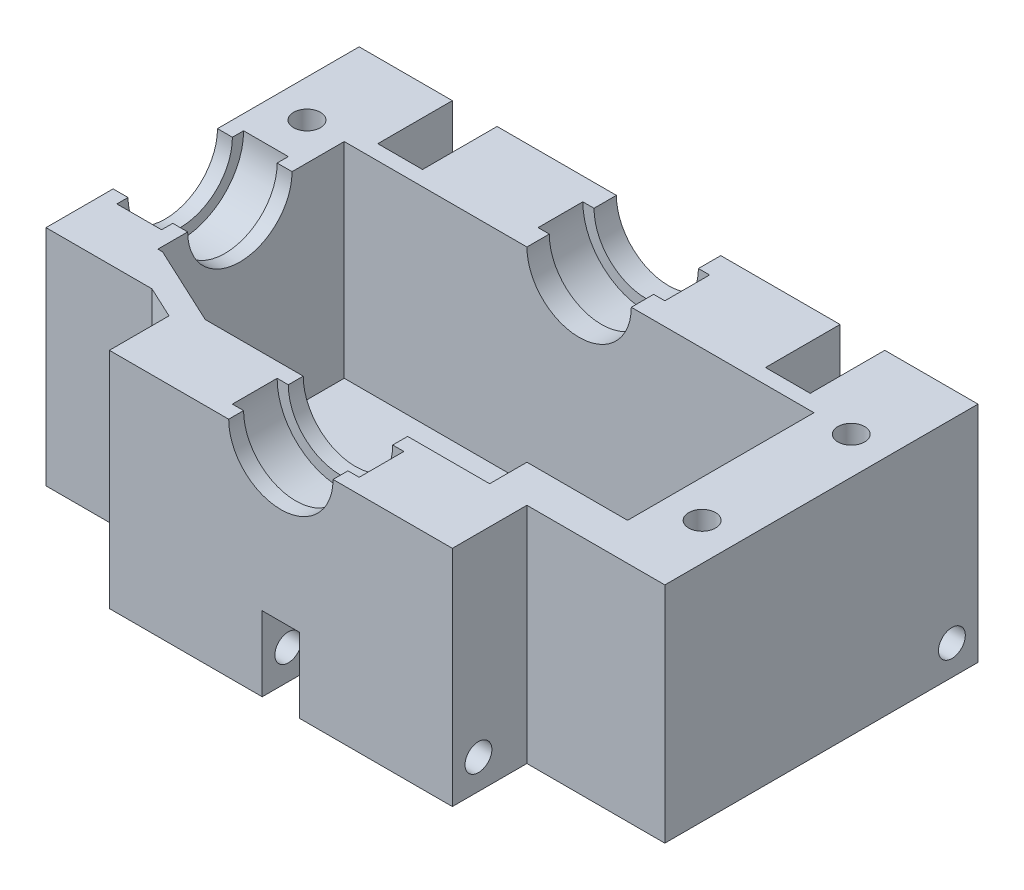
SolidWorks part; units mm, degrees
note: The reader was unsure of these and kept them because the rebuilt part matched: shared geometry of "Sketch1<4>", "Sketch3<4>", "Sketch17<3>".
material "PLA"
ref_plane "Front Plane" through (0, 0, 0) normal (0, 0, 1) x (1, 0, 0)
ref_plane "Top Plane" through (0, 0, 0) normal (0, 1, 0) x (1, 0, 0)
ref_plane "Right Plane" through (0, 0, 0) normal (1, 0, 0) x (0, 0, -1)
sketch "Sketch1" plane through (0, 0, 0) normal (0, 1, 0) x (1, 0, 0)
  line L0 (-41.5, 12) -> (41.5, 12)
  line L1 (41.5, 12) -> (41.5, -15)
  line L2 (41.5, -15) -> (31.5, -15) construction
  line L4 (23, -40) -> (-23, -40)
  line L5 (-23, -40) -> (-23, -30)
  line L6 (-23, -15) -> (-31.5, -15) construction
  line L7 (-41.5, -15) -> (-41.5, 12)
  line L8 (-31.5, 0) -> (-31.5, -10)
  line L9 (-31.5, -10) -> (-18, -10) construction
  line L10 (-18, -25) -> (-18, -30)
  line L11 (-18, -30) -> (18, -30)
  line L12 (18, -30) -> (18, -25)
  line L13 (18, -10) -> (31.5, -10) construction
  line L14 (31.5, -10) -> (31.5, 0)
  line L15 (31.5, 0) -> (-31.5, 0)
  line L16 (0, 31.084) -> (0, 48.5118) construction
  line L17 (-10, -35) -> (10, -35) construction
  line L18 (-10, 6) -> (10, 6) construction
  line L23 (23, -30) -> (41.5, -30)
  line L24 (41.5, -30) -> (41.5, -15)
  line L25 (23, -30) -> (23, -40)
  line L26 (31.5, -10) -> (31.5, -25)
  line L27 (31.5, -25) -> (18, -25)
  line L28 (-41.5, -15) -> (-41.5, -30)
  line L29 (-41.5, -30) -> (-23, -30)
  line L30 (-31.5, -10) -> (-31.5, -25)
  line L31 (-31.5, -25) -> (-18, -25)
  line L32 (-31.5, -15) -> (-41.5, -15) construction
  line L33 (-18, -10) -> (-18, -25) construction
  line L34 (-23, -25) -> (-23, -15) construction
  line L35 (-23, -30) -> (-23, -25) construction
  line L36 (31.5, -15) -> (23, -15) construction
  line L37 (23, -15) -> (23, -25) construction
  line L38 (18, -25) -> (18, -10) construction
  line L39 (23, -25) -> (23, -30) construction
  point P17 (0, -40)
  point P19 (0, -30)
  point P20 (0, 0)
  point P21 (0, 12)
  point P22 (-10, 6)
  point P23 (10, 6)
  point P24 (10, -35)
  point P25 (-10, -35)
  dimension "D1" = 63
  dimension "D2" = 10
  dimension "D3" = 12
  dimension "D4" = 10
  dimension "D5" = 10
  dimension "D6" = 5
  dimension "D7" = 5
  dimension "D8" = 10
  dimension "D9" = 20
  dimension "D10" = 36
  dimension "D11" = 10
  dimension "D13" = 5
extrude "Boss-Extrude1" add sketch "Sketch1" along normal blind 30 contours L0 L1 L24 L23 L25 L4 L5 L29 L28 L7
extrude "Cut-Extrude2" cut sketch "Sketch1<4>" against normal blind 27.5 from surface contours L11 L16 L15 L8 L9 L10 | L16 L11 L12 L13 L14 L15
sketch "Sketch1<4>" plane through (0, 0, 0) normal (0, 1, 0) x (1, 0, 0) same geometry as "Sketch1"
sketch "Sketch3" plane through (0, 0, 40) normal (0, 0, 1) x (1, 0, 0)
  line L0 (23, 30) -> (-23, 30) construction
  circle A0 centre (0, 30) radius 8.5
  circle A1 centre (0, 30) radius 7
  line M3 (23, 30) -> (-23, 30)
  dimension "D1" = 17
  dimension "D2" = 14
extrude "Cut-Extrude3" cut sketch "Sketch3" against normal blind 6 from offset 2 contours A0 offset against normal yes
sketch "Sketch4" plane through (0, 0, -12) normal (0, 0, -1) x (-1, 0, 0)
  line L2 (41.5, 30) -> (-41.5, 30) construction
  circle A0 centre (0, 30) radius 8.5
  circle A1 centre (0, 30) radius 6.5
  dimension "D1" = 17
  dimension "D2" = 13
extrude "Cut-Extrude4" cut sketch "Sketch4" against normal blind 6 from offset 3 contours A0 offset against normal yes
extrude "Cut-Extrude6" cut sketch "Sketch3<4>" against normal through all contours A1 M3 | A1 M3
sketch "Sketch3<4>" plane through (0, 0, 40) normal (0, 0, 1) x (1, 0, 0) same geometry as "Sketch3"
sketch "Sketch16" plane through (0, 0, -12) normal (0, 0, -1) x (-1, 0, 0)
  line L0 (23, 30) -> (23, 0) construction
  line L1 (29, 30) -> (29, 0)
  line L3 (-23, 30) -> (-23, 0)
  line L5 (-7, 30) -> (-41.5, 30)
  line L6 (-41.5, 30) -> (-41.5, 0)
  line L7 (-41.5, 0) -> (41.5, 0)
  line L8 (41.5, 0) -> (41.5, 30)
  line L9 (41.5, 30) -> (7, 30)
  line L10 (-7, 30) -> (-41.5, 30)
  line L11 (-41.5, 30) -> (-41.5, 0)
  line L12 (-41.5, 0) -> (41.5, 0)
  line L13 (41.5, 0) -> (41.5, 30)
  line L14 (41.5, 30) -> (7, 30)
  line L15 (-29, 30) -> (-29, 0)
  line L16 (-23, 30) -> (-23, 0) construction
  line L18 (23, 30) -> (23, 0)
  arc A1 (-7, 30) -> (7, 30) centre (0, 30) ccw
  arc A2 (-7, 30) -> (7, 30) centre (0, 30) ccw
  dimension "D2" = 6
  dimension "D3" = 6
  dimension "D1" = 0
extrude "Cut-Extrude7" cut sketch "Sketch16" against normal blind 10
sketch "Sketch17" plane through (-41.5, 0, 0) normal (1, 0, 0) x (0, 0, -1)
  line L0 (12, 30) -> (-30, 30) construction
  circle A0 centre (-14, 30) radius 8.5
  circle A1 centre (-14, 30) radius 7
  line M14 (-30, 30) -> (12, 30)
  dimension "D1" = 17
  dimension "D2" = 14
  dimension "D3" = 26
extrude "Cut-Extrude8" cut sketch "Sketch17" along normal blind 6 from offset 2 contours A0
extrude "Cut-Extrude9" cut sketch "Sketch17<3>" along normal up to surface (10 mm away) contours A1 M14 | A1 M14 up to face at (-31.5, 16.25, 12.5)
sketch "Sketch17<3>" plane through (-41.5, 0, 0) normal (1, 0, 0) x (0, 0, -1) same geometry as "Sketch17"
chamfer "Chamfer1" distance 2 angle 65 1 edges at (-23, 15, 30)
chamfer "Chamfer2" distance 6 angle 65 1 edges at (-18, 16.25, 25)
sketch "Sketch19" plane through (0, 0, 0) normal (0, -1, 0) x (1, 0, 0)
  line L1 (2.5, -12) -> (-2.5, -12)
  line L2 (2.5, -12) -> (2.5, -5)
  line L3 (2.5, -5) -> (-2.5, -5)
  line L4 (-2.5, -12) -> (-2.5, -5)
  line L6 (-2.5, 40) -> (2.5, 40)
  line L7 (-2.5, 40) -> (-2.5, 33)
  line L8 (-2.5, 33) -> (2.5, 33)
  line L9 (2.5, 40) -> (2.5, 33)
  line L10 (23, 40) -> (-23, 40) construction
  line L11 (-23, -12) -> (23, -12) construction
  point P20 (0, 33)
  point P23 (0, -5)
  dimension "D1" = 5
  dimension "D2" = 7
  dimension "D3" = 5
  dimension "D4" = 7
extrude "Cut-Extrude11" cut sketch "Sketch19" against normal blind 10
sketch "Sketch20" plane through (41.5, 0, 0) normal (1, 0, 0) x (0, 0, -1)
  line L0 (-40, 0) -> (-33, 0) construction
  line L1 (5, 0) -> (12, 0) construction
  line L2 (-30, 0) -> (12, 0) construction
  point P0 (8.5, 4)
  point P1 (-36.5, 4)
  point P5 (-36.5, 0)
  point P9 (8.5, 0)
  dimension "D1" = 4
hole_wizard "M3 Clearance Hole1" positions "Sketch21" profile "Sketch22" hole size "M3" standard "ISO" end condition through all
sketch "Sketch21" plane through (41.5, 0, 0) normal (1, 0, 0) x (0, 0, -1)
  point P0 (8.5, 4)
  point P3 (-36.5, 4)
sketch "Sketch22" plane through (41.5, 4, -8.5) normal (0, 1, 0) x (0, 0, -1)
  line L0 (0, 0) -> (0, 83)
  line L1 (0, 83) -> (1.8, 83)
  line L2 (1.8, 83) -> (1.8, 0)
  line L5 (1.8, 0) -> (0, 0)
  line L11 (0, -6.35) -> (0, 107.95) construction
  dimension "Thru Hole Dia." = 3.6
  dimension "Thru Hole Depth" = 83
sketch "Sketch23" plane through (0, 30, 0) normal (0, 1, 0) x (1, 0, 0)
  line L0 (36.5, 0) -> (36.5, -20) construction
  line L1 (-36.5, -1.8525) -> (-36.5, -16.1872) construction
  line L2 (-41.5, -7) -> (-41.5, 12) construction
  line L3 (-31.5, 0) -> (-31.5, -25) construction
  line L4 (31.5, 0) -> (31.5, -25) construction
  line L5 (41.5, 12) -> (41.5, -30) construction
  line L6 (29, 12) -> (41.5, 12) construction
  point P0 (36.5, 0)
  point P1 (36.5, -20)
  point P2 (-36.5, 0)
  dimension "D1" = 20
  dimension "D2" = 12
hole_wizard "M3 Clearance Hole2" positions "Sketch24" profile "Sketch26" hole size "M3" standard "ISO" end condition through all
sketch "Sketch24" plane through (0, 30, 0) normal (0, 1, 0) x (1, 0, 0)
  point P0 (-36.5, 0)
  point P3 (36.5, 0)
  point P6 (36.5, -20)
sketch "Sketch26" plane through (-36.5, 30, 0) normal (1, 0, 0) x (0, 0, 1)
  line L0 (0, 0) -> (0, 30)
  line L1 (0, 30) -> (1.8, 30)
  line L2 (1.8, 30) -> (1.8, 0)
  line L5 (1.8, 0) -> (0, 0)
  line L11 (0, -6.35) -> (0, 107.95) construction
  dimension "Thru Hole Dia." = 3.6
  dimension "Thru Hole Depth" = 30
